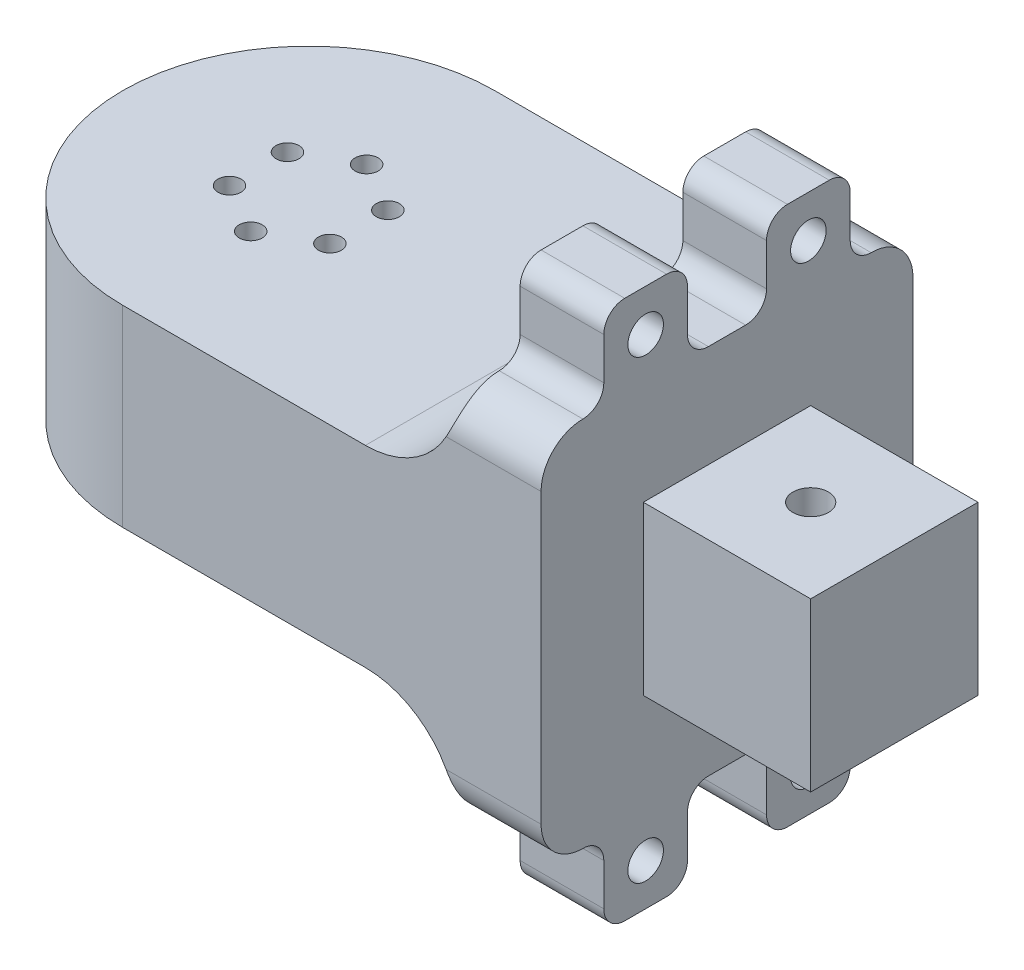
SolidWorks part; units mm, degrees
ref_plane "Front Plane" through (0, 0, 0) normal (0, 0, 1) x (1, 0, 0)
ref_plane "Top Plane" through (0, 0, 0) normal (0, 1, 0) x (1, 0, 0)
ref_plane "Right Plane" through (0, 0, 0) normal (1, 0, 0) x (0, 0, -1)
sketch "Sketch1" plane through (0, 0, 0) normal (0, 1, 0) x (1, 0, 0)
  line L0 (0, 44.45) -> (80, 44.45)
  line L1 (80, 44.45) -> (80, -44.45)
  line L2 (80, -44.45) -> (0, -44.45)
  arc A0 (0, 44.45) -> (0, -44.45) centre (0, 0) ccw
  dimension "D1" = 44.45
  dimension "D2" = 80
extrude "Boss-Extrude1" add sketch "Sketch1" along normal blind 46
sketch "Sketch2" plane through (0, 0, 0) normal (0, -1, 0) x (-1, 0, 0)
  line L1 (0, -13.8564) -> (12, -6.9282)
  line L2 (12, -6.9282) -> (12, 6.9282)
  line L3 (12, 6.9282) -> (0, 13.8564)
  line L4 (0, 13.8564) -> (-12, 6.9282)
  line L5 (-12, 6.9282) -> (-12, -6.9282)
  line L6 (-12, -6.9282) -> (0, -13.8564)
  circle A0 centre (0, 0) radius 12 construction
  circle A1 centre (0, -13.8564) radius 2.75
  circle A2 centre (12, -6.9282) radius 2.75
  circle A3 centre (12, 6.9282) radius 2.75
  circle A4 centre (0, 13.8564) radius 2.75
  circle A5 centre (-12, 6.9282) radius 2.75
  circle A6 centre (-12, -6.9282) radius 2.75
extrude "Cut-Extrude2" cut sketch "Sketch2" against normal blind 76 contours L6 A1 L1 | L5 A6 L6 | L4 A5 L5 | L3 A4 L4 | L2 A3 L3 | L1 A2 L2 | L2 A2 L1 | L1 A1 L6 | L6 A6 L5 | L5 A5 L4 | L4 A4 L3 | L3 A3 L2 region at (0, 0, 12.3403) region at (0, 0, 14.6145) region at (-10.687, 0, 6.1701) region at (-12.6565, 0, 7.3072) region at (12.6565, 0, 7.3072) region at (10.687, 0, 6.1701) region at (-10.687, 0, -6.1701) region at (-12.6565, 0, -7.3072) region at (12.6565, 0, -7.3072) region at (10.687, 0, -6.1701) region at (0, 0, -12.3403) region at (0, 0, -14.6145)
sketch "Sketch3" plane through (80, 0, 0) normal (1, 0, 0) x (0, 0, -1)
  line L2 (-44.45, 67.45) -> (-44.45, -21.45)
  line L4 (-44.45, 67.45) -> (44.45, 67.45)
  line L5 (44.45, 67.45) -> (44.45, -21.45)
  line L6 (-44.45, -21.45) -> (44.45, -21.45)
  dimension "D1" = 88.9
  dimension "D2" = 88.9
extrude "Boss-Extrude2" add sketch "Sketch3" along normal blind 20
fillet "Fillet1" radius 22 2 edges at (80, 46, 0) (80, 0, 0)
sketch "Sketch5" plane through (100, 0, 0) normal (1, 0, 0) x (0, 0, -1)
  line L0 (0, 23) -> (0, 43)
  line L1 (0, 43) -> (-20, 43)
  line L2 (-20, 43) -> (-20, 3)
  line L3 (-20, 3) -> (20, 3)
  line L4 (20, 3) -> (20, 43)
  line L5 (20, 43) -> (0, 43)
  dimension "D1" = 20
extrude "Boss-Extrude3" add sketch "Sketch5" along normal blind 40 contours L4 L5 L1 L2 L3 region at (100, 42.4343, -10)
sketch "Sketch6" plane through (0, 43, 0) normal (0, 1, 0) x (1, 0, 0)
  line L0 (140, 20) -> (140, -20) construction
  circle A0 centre (120, 0) radius 4.25
  dimension "D1" = 20
extrude "Cut-Extrude3" cut sketch "Sketch6" against normal blind 67
sketch "Sketch7" plane through (0, 67.45, 0) normal (0, 1, 0) x (1, 0, 0)
  line L0 (80, 44.45) -> (80, -44.45) construction
  line L1 (80, 29.45) -> (100, 29.45)
  line L2 (80, 29.45) -> (80, 9.45)
  line L3 (80, 9.45) -> (100, 9.45)
  line L4 (100, 29.45) -> (100, 9.45)
  line L5 (100, 20) -> (100, -20) construction
  line L6 (100, 44.45) -> (80, 44.45) construction
  line L7 (100, 44.45) -> (100, -44.45) construction
  line L8 (80, -9.45) -> (100, -9.45)
  line L9 (80, -9.45) -> (80, -29.45)
  line L10 (80, -29.45) -> (100, -29.45)
  line L11 (100, -9.45) -> (100, -29.45)
  line L12 (100, -44.45) -> (80, -44.45) construction
  dimension "D1" = 20
  dimension "D2" = 15
  dimension "D3" = 20
  dimension "D4" = 15
extrude "Boss-Extrude4" add sketch "Sketch7" along normal blind 20
sketch "Sketch8" plane through (0, -21.45, 0) normal (0, -1, 0) x (1, 0, 0)
  line L0 (80, 44.45) -> (80, -44.45) construction
  line L1 (80, 29.45) -> (100, 29.45)
  line L2 (80, 29.45) -> (80, 9.45)
  line L3 (80, 9.45) -> (100, 9.45)
  line L4 (100, 29.45) -> (100, 9.45)
  line L5 (100, 44.45) -> (100, -44.45) construction
  line L6 (100, 44.45) -> (80, 44.45) construction
  line L7 (100, 20) -> (100, -20) construction
  line L8 (80, -29.45) -> (100, -29.45)
  line L9 (80, -29.45) -> (80, -9.45)
  line L10 (80, -9.45) -> (100, -9.45)
  line L11 (100, -29.45) -> (100, -9.45)
  line L12 (100, -44.45) -> (80, -44.45) construction
  dimension "D1" = 20
  dimension "D2" = 15
  dimension "D3" = 20
  dimension "D4" = 15
extrude "Boss-Extrude5" add sketch "Sketch8" along normal blind 20
fillet "Fillet2" radius 5 16 edges at (90, -41.45, -29.45) (90, -41.45, 29.45) (90, 87.45, -9.45) (90, 87.45, -29.45) (90, 87.45, 9.45) (90, 87.45, 29.45) (90, -41.45, -9.45) (90, -41.45, 9.45) (90, -21.45, -29.45) (90, -21.45, -9.45) (90, -21.45, 9.45) (90, -21.45, 29.45) (90, 67.45, 29.45) (90, 67.45, -29.45) (90, 67.45, -9.45) (90, 67.45, 9.45)
fillet "Fillet3" radius 10 4 edges at (90, -21.45, -44.45) (90, 67.45, -44.45) (90, 67.45, 44.45) (90, -21.45, 44.45)
sketch "Sketch10" plane through (80, 0, 0) normal (-1, 0, 0) x (0, 0, 1)
  line L0 (-24.45, 87.45) -> (-14.45, 87.45) construction
  line L1 (-9.45, 82.45) -> (-9.45, 72.45) construction
  line L2 (9.45, 82.45) -> (9.45, 72.45) construction
  line L3 (14.45, 87.45) -> (24.45, 87.45) construction
  line L4 (29.45, -36.45) -> (29.45, -26.45) construction
  line L5 (24.45, -41.45) -> (14.45, -41.45) construction
  line L6 (-14.45, -41.45) -> (-24.45, -41.45) construction
  line L7 (-29.45, -36.45) -> (-29.45, -26.45) construction
  circle A0 centre (-19.45, 77.45) radius 4.25
  circle A1 centre (19.45, 77.45) radius 4.25
  circle A2 centre (19.45, -31.45) radius 4.25
  circle A3 centre (-19.45, -31.45) radius 4.25
  dimension "D1" = 10
  dimension "D2" = 10
  dimension "D3" = 10
  dimension "D4" = 10
  dimension "D5" = 10
  dimension "D6" = 10
  dimension "D7" = 10
  dimension "D8" = 10
extrude "Cut-Extrude4" cut sketch "Sketch10" against normal blind 20
